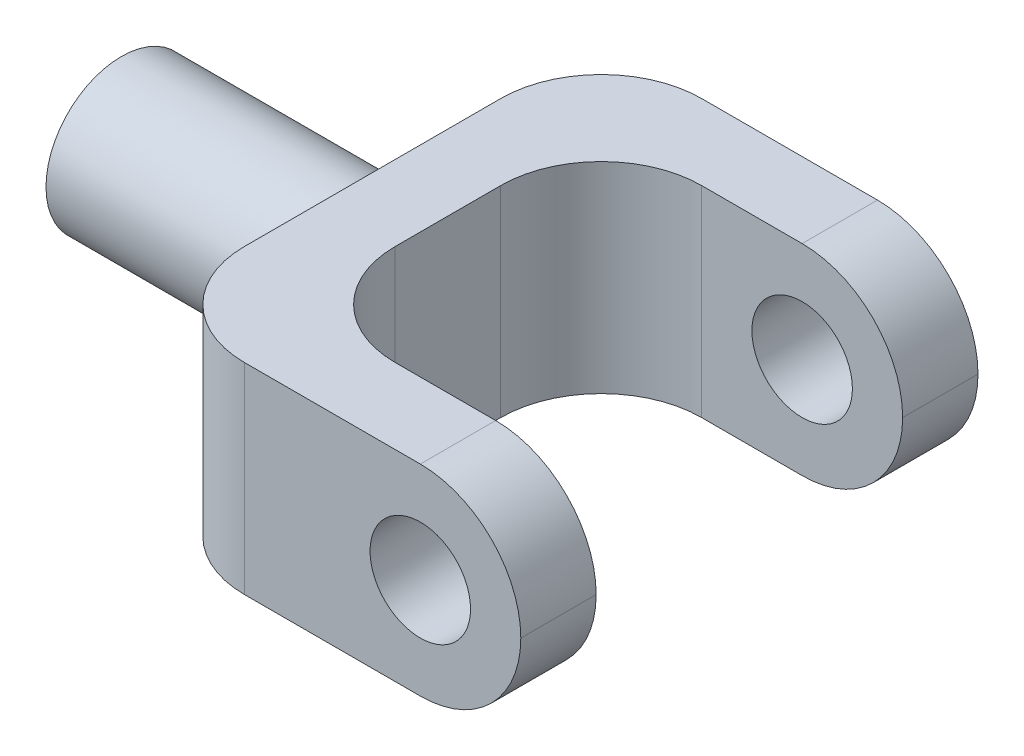
SolidWorks part; units mm, degrees
ref_plane "Front Plane" through (0, 0, 0) normal (0, 0, 1) x (1, 0, 0)
ref_plane "Top Plane" through (0, 0, 0) normal (0, 1, 0) x (1, 0, 0)
ref_plane "Right Plane" through (0, 0, 0) normal (1, 0, 0) x (0, 0, -1)
sketch "Sketch1" plane through (0, 0, 0) normal (0, 1, 0) x (1, 0, 0)
  line L0 (1.5, -6.1) -> (1.5, 6.1)
  line L1 (1.5, 6.1) -> (13.5, 6.1)
  line L2 (13.5, 6.1) -> (13.5, 9.1)
  line L3 (13.5, 9.1) -> (-1.5, 9.1)
  line L4 (-1.5, 9.1) -> (-1.5, -9.1)
  line L5 (0, 0) -> (1.5, 0) construction
  line L6 (0, 0) -> (-1.5, 0) construction
  line L7 (13.5, -6.1) -> (13.5, -9.1)
  line L8 (13.5, -9.1) -> (-1.5, -9.1)
  line L9 (1.5, -6.1) -> (13.5, -6.1)
  dimension "D1" = 3
  dimension "D2" = 3
  dimension "D3" = 6.1
  dimension "D4" = 12
extrude "Boss-Extrude1" add sketch "Sketch1" along normal blind 8
sketch "Sketch2" plane through (0, 0, 9.1) normal (0, 0, 1) x (1, 0, 0)
  line L0 (13.5, 4) -> (9.5, 4) construction
  line L1 (13.5, 8) -> (13.5, 0) construction
  line L2 (9.5, 4) -> (9.5, 8) construction
  line L3 (-1.5, 8) -> (13.5, 8) construction
  circle A0 centre (9.5, 4) radius 2
  dimension "D1" = 4
extrude "Cut-Extrude1" cut sketch "Sketch2" against normal through all
sketch "Sketch3" plane through (-1.5, 0, 0) normal (-1, 0, 0) x (0, 0, 1)
  line L0 (-9.1, 4) -> (9.1, 4) construction
  line L1 (-9.1, 8) -> (-9.1, 0) construction
  line L2 (9.1, 8) -> (9.1, 0) construction
  line L3 (0, 8) -> (0, 0) construction
  line L4 (-9.1, 8) -> (9.1, 8) construction
  line L5 (-9.1, 0) -> (9.1, 0) construction
  circle A0 centre (0, 4) radius 3
  dimension "D1" = 6
extrude "Boss-Extrude2" add sketch "Sketch3" along normal blind 10
fillet "Fillet1" radius 4 4 edges at (13.5, 8, -7.6) (13.5, 0, -7.6) (13.5, 0, 7.6) (13.5, 8, 7.6)
fillet "Fillet2" radius 4 4 edges at (-1.5, 4, -9.1) (-1.5, 4, 9.1) (1.5, 4, 6.1) (1.5, 4, -6.1)
